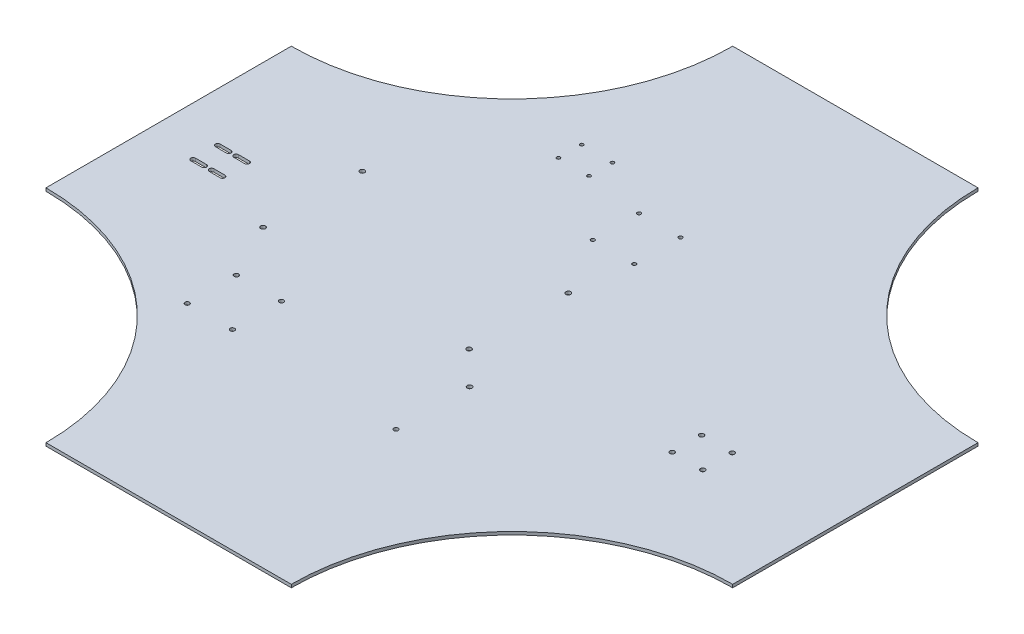
SolidWorks part; units mm, degrees
material "6061 Alloy"
ref_plane "Front Plane" through (0, 0, 0) normal (0, 0, 1) x (1, 0, 0)
ref_plane "Top Plane" through (0, 0, 0) normal (0, 1, 0) x (1, 0, 0)
ref_plane "Right Plane" through (0, 0, 0) normal (1, 0, 0) x (0, 0, -1)
sketch "Sketch1" plane through (0, 0, 0) normal (0, 1, 0) x (1, 0, 0)
  line L9 (-127, -355.6) -> (127, -355.6)
  line L10 (-355.6, -127) -> (-355.6, 127)
  line L11 (-127, 355.6) -> (127, 355.6)
  line L12 (355.6, -127) -> (355.6, 127)
  line L13 (-193.9554, -193.9554) -> (193.9554, 193.9554) construction
  line L14 (-193.9554, 193.9554) -> (193.9554, -193.9554) construction
  arc A8 (-355.6, 127) -> (-127, 355.6) centre (-355.6, 355.6) ccw
  arc A9 (127, 355.6) -> (355.6, 127) centre (355.6, 355.6) ccw
  arc A10 (355.6, -127) -> (127, -355.6) centre (355.6, -355.6) ccw
  arc A11 (-127, -355.6) -> (-355.6, -127) centre (-355.6, -355.6) ccw
  point P0 (0, 0)
  point P1 (0, 0)
  point P2 (0, 0)
  dimension "D3" = 457.2
  dimension "D4" = 457.2
  dimension "D5" = 457.2
  dimension "D6" = 457.2
  dimension "D1" = 711.2
  dimension "D2" = 711.2
extrude "Boss-Extrude1" add sketch "Sketch1" along normal blind 3.175
sketch "Sketch2" plane through (0, 3.175, 0) normal (0, 1, 0) x (1, 0, 0)
  line L0 (-304.8, 2.413) -> (-293.37, 2.413)
  line L1 (-304.8, -22.987) -> (-293.37, -22.987)
  line L2 (-293.37, -2.413) -> (-304.8, -2.413)
  line L3 (-285.75, -2.413) -> (-274.32, -2.413)
  line L4 (-285.75, -22.987) -> (-274.32, -22.987)
  line L5 (-274.32, 2.413) -> (-285.75, 2.413)
  line L6 (-293.37, -27.813) -> (-304.8, -27.813)
  line L7 (-355.6, 127) -> (-355.6, -127) construction
  line L8 (-274.32, -27.813) -> (-285.75, -27.813)
  arc A0 (-293.37, -2.413) -> (-293.37, 2.413) centre (-293.37, 0) ccw
  arc A1 (-274.32, -2.413) -> (-274.32, 2.413) centre (-274.32, 0) ccw
  arc A2 (-274.32, -27.813) -> (-274.32, -22.987) centre (-274.32, -25.4) ccw
  arc A3 (-293.37, -27.813) -> (-293.37, -22.987) centre (-293.37, -25.4) ccw
  arc A4 (-285.75, 2.413) -> (-285.75, -2.413) centre (-285.75, 0) ccw
  arc A5 (-304.8, 2.413) -> (-304.8, -2.413) centre (-304.8, 0) ccw
  arc A6 (-304.8, -22.987) -> (-304.8, -27.813) centre (-304.8, -25.4) ccw
  arc A7 (-285.75, -22.987) -> (-285.75, -27.813) centre (-285.75, -25.4) ccw
  dimension "D1" = 4.826
  dimension "D2" = 4.826
  dimension "D3" = 4.826
  dimension "D4" = 4.826
  dimension "D5" = 4.826
  dimension "D6" = 4.826
  dimension "D7" = 4.826
  dimension "D8" = 4.826
  dimension "D9" = 11.43
  dimension "D10" = 11.43
  dimension "D11" = 11.43
  dimension "D12" = 11.43
  dimension "D13" = 19.05
  dimension "D14" = 19.05
  dimension "D15" = 25.4
  dimension "D16" = 25.4
  dimension "D17" = 0
  dimension "D18" = 50.8
extrude "Cut-Extrude1" cut sketch "Sketch2" against normal through all both and the other way through all
sketch "Sketch4" plane through (0, 3.175, 0) normal (0, 1, 0) x (1, 0, 0)
  circle A0 centre (237.49, -9.4302) radius 2.413
  circle A1 centre (205.74, -9.4302) radius 2.413
  circle A2 centre (237.49, -39.9102) radius 2.413
  circle A3 centre (205.74, -39.9102) radius 2.413
extrude "Cut-Extrude2" cut sketch "Sketch4" against normal through all
sketch "Sketch5" plane through (0, 0, 0) normal (0, -1, 0) x (1, 0, 0)
  circle A0 centre (-207.7901, 50.0166) radius 2.5
  circle A1 centre (-206.624, -51.5767) radius 2.5
  circle A2 centre (8.0956, 52.4945) radius 2.478
  circle A3 centre (9.2617, -49.0988) radius 2.5
extrude "Cut-Extrude3" cut sketch "Sketch5" against normal through all
sketch "Sketch6" plane through (0, 0, 0) normal (0, -1, 0) x (1, 0, 0)
  circle A0 centre (-131.9657, 157.5947) radius 2.3218
  circle A1 centre (-131.9657, 106.7947) radius 2.3218
  circle A2 centre (-178.7006, 106.7947) radius 2.3218
  circle A3 centre (-178.7006, 157.5947) radius 2.3218
  circle A4 centre (42.2659, 162.3375) radius 2.3082
  circle A5 centre (42.2659, 86.1375) radius 2.5
  circle A6 centre (17.3717, -109.2657) radius 1.905
  circle A7 centre (-25.6811, -109.3842) radius 1.905
  circle A8 centre (-25.5498, -157.136) radius 1.905
  circle A9 centre (17.503, -157.0152) radius 1.905
  circle A10 centre (-84.8824, -188.8713) radius 1.75
  circle A11 centre (-85.0918, -164.8722) radius 1.75
  circle A12 centre (-116.8812, -189.1505) radius 1.75
  circle A13 centre (-117.0906, -165.1514) radius 1.75
extrude "Cut-Extrude4" cut sketch "Sketch6" against normal through all
